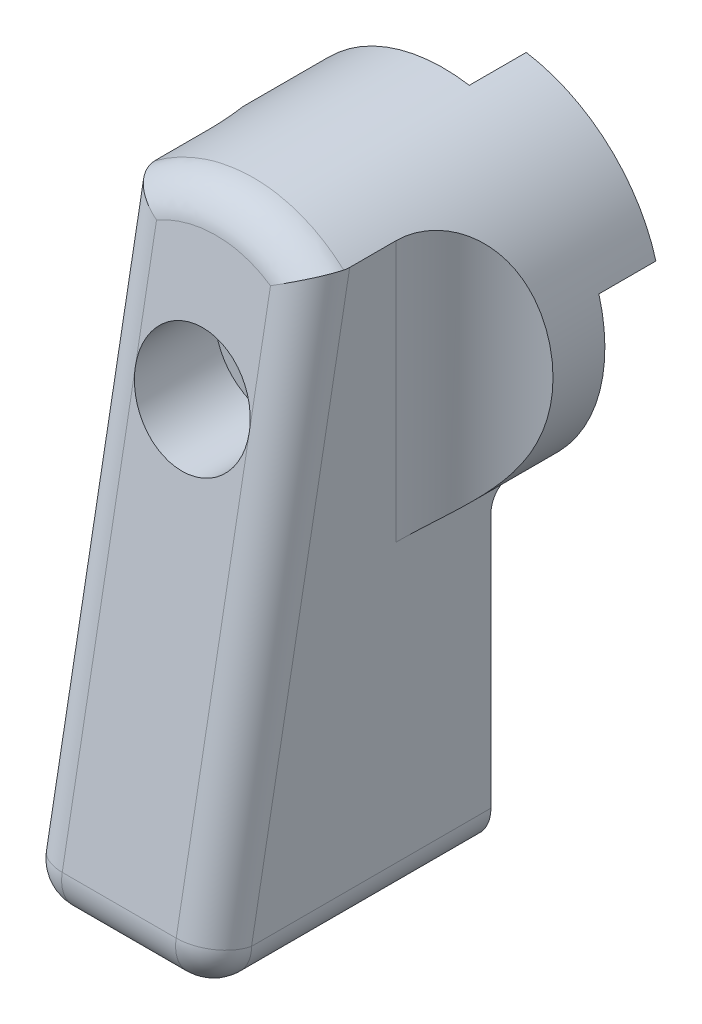
SolidWorks part; units mm, degrees
note: The reader was unsure of these and kept them because the rebuilt part matched: shared geometry of "Эскиз1<5>", "Эскиз1<6>".
ref_plane "Спереди" through (0, 0, 0) normal (0, 0, 1) x (1, 0, 0)
ref_plane "Сверху" through (0, 0, 0) normal (0, 1, 0) x (1, 0, 0)
ref_plane "Справа" through (0, 0, 0) normal (1, 0, 0) x (0, 0, -1)
sketch "Эскиз1" plane through (0, 0, 0) normal (0, 0, 1) x (1, 0, 0)
  line L0 (1.0405, 6.4162) -> (1.3607, 8.3904)
  line L1 (6.2596, 1.7513) -> (8.1857, 2.2902)
  line L2 (-1.0405, -6.4162) -> (-1.3607, -8.3904)
  line L3 (-6.2596, -1.7513) -> (-8.1857, -2.2902)
  line L5 (-3.25, -4) -> (3.25, -4)
  line L6 (-3.25, -4) -> (-3.25, 4)
  line L7 (-3.25, 4) -> (3.25, 4)
  line L8 (3.25, -4) -> (3.25, 4)
  line L9 (-3.25, -4) -> (3.25, 4) construction
  line L10 (-3.25, 4) -> (3.25, -4) construction
  circle A0 centre (0, 0) radius 8.5
  circle A1 centre (0, 0) radius 4
  circle A2 centre (0, 0) radius 6.5
  point P16 (0, 0)
  dimension "D1" = 17
  dimension "D2" = 8
  dimension "D3" = 2
  dimension "D4" = 7
  dimension "D5" = 9.1538
  dimension "D7" = 6.5
  dimension "D6" = 2
extrude "Бобышка-Вытянуть1" add sketch "Эскиз1" along normal blind 2.5 contours A1 | A0
extrude "Бобышка-Вытянуть2" add sketch "Эскиз1<5>" against normal blind 3 contours A2 L1 A0 L0 | A2 L3 A0 L2
sketch "Эскиз1<5>" plane through (0, 0, 0) normal (0, 0, 1) x (1, 0, 0) same geometry as "Эскиз1"
sketch "Эскиз2" plane through (0, 0, 2.5) normal (0, 0, 1) x (1, 0, 0)
  line L0 (-5, 8.5) -> (5, 8.5)
  line L1 (-5, 8.5) -> (-5, -23.5)
  line L2 (5, 8.5) -> (5, -23.5)
  line L3 (-5, -23.5) -> (5, -23.5)
  line L4 (0, 8.5) -> (0, -23.5) construction
  circle A0 centre (0, 0) radius 8.5 construction
  circle A1 centre (0, 0) radius 8.5
  circle M6 centre (0, 0) radius 8.5
  arc M7 (-3.25, 2.3318) -> (3.25, 2.3318) centre (0, 0) cw
  line M8 (3.25, 2.3318) -> (3.25, -2.3318)
  arc M9 (3.25, -2.3318) -> (-3.25, -2.3318) centre (0, 0) cw
  line M10 (-3.25, -2.3318) -> (-3.25, 2.3318)
  dimension "D1" = 32
  dimension "D2" = 10
extrude "Бобышка-Вытянуть3" add sketch "Эскиз2" along normal blind 15 contours L4 A1 L2 M6 M7 M8 M9 | L4 L1 M6 M9 M10 M7 | A1 L4 L3 L2 | L4 L1 L3 M6 | L4 M7 M9 M8 | L4 M7 M10 M9
sketch "Эскиз6" plane through (0, 0, 17.5) normal (0, 0, 1) x (1, 0, 0)
  circle A0 centre (0, 0) radius 3
  dimension "D1" = 6
sketch "Эскиз3" plane through (-5, 0, 0) normal (-1, 0, 0) x (0, 0, 1)
  line L0 (2.5, -23.5) -> (2.5, 9.1456)
  line L1 (2.5, 9.1456) -> (11.5564, 9.1456)
  line L2 (11.5564, 9.1456) -> (17.5, -23.5)
  line L3 (17.5, -23.5) -> (2.5, -23.5)
  line L4 (11.5564, 9.1456) -> (17.5, 9.1456)
  line L5 (17.5, 9.1456) -> (17.5, -23.5)
  line L6 (2.5, -23.5) -> (2.5, 9.1456)
  line L7 (2.5, -23.5) -> (17.5, -23.5)
  line L8 (2.5, 9.1456) -> (17.5, 9.1456)
  line L9 (17.5, -23.5) -> (17.5, 9.1456)
  line M13 (17.5, -23.5) -> (17.5, 6.8739)
  line M14 (17.5, 6.8739) -> (2.5, 6.8739)
extrude "Вырез-Вытянуть1" cut sketch "Эскиз3" against normal blind 10 contours L2 M14 M13 | L5 L4 L2 M14
fillet "Скругление4" radius 2 6 edges at (0, 8.5, 11.674) (5, -8.3131, 14.735) (5, -23.5, 10) (-5, -8.3131, 14.735) (-5, -23.5, 10) (0, -23.5, 17.5)
fillet "Скругление5" radius 5 2 edges at (5, 0, 2.5) (-5, 0, 2.5)
fillet "Скругление6" radius 1 1 edges at (0, -8.5, 2.5)
extrude "Вырез-Вытянуть2" cut sketch "Эскиз1<6>" along normal blind 6.5 contours L8 A1 L6
sketch "Эскиз1<6>" plane through (0, 0, 0) normal (0, 0, 1) x (1, 0, 0) same geometry as "Эскиз1"
sketch "Эскиз4" plane through (0, 0, 6.5) normal (0, 0, -1) x (-1, 0, 0)
  circle A0 centre (0, 0) radius 1.75
  dimension "D1" = 3.5
extrude "Вырез-Вытянуть3" cut sketch "Эскиз4" against normal blind 9.5
sketch "Эскиз5" plane through (0, 0, 6.5) normal (0, 0, -1) x (-1, 0, 0)
  circle A0 centre (0, 0) radius 3
  dimension "D1" = 6
extrude "Вырез-Вытянуть5" cut sketch "Эскиз6" against normal blind 8.5 contours A0
chamfer "Фаска2" distance 0.5 angle 45 1 edges at (-1.75, 0, 6.5)
